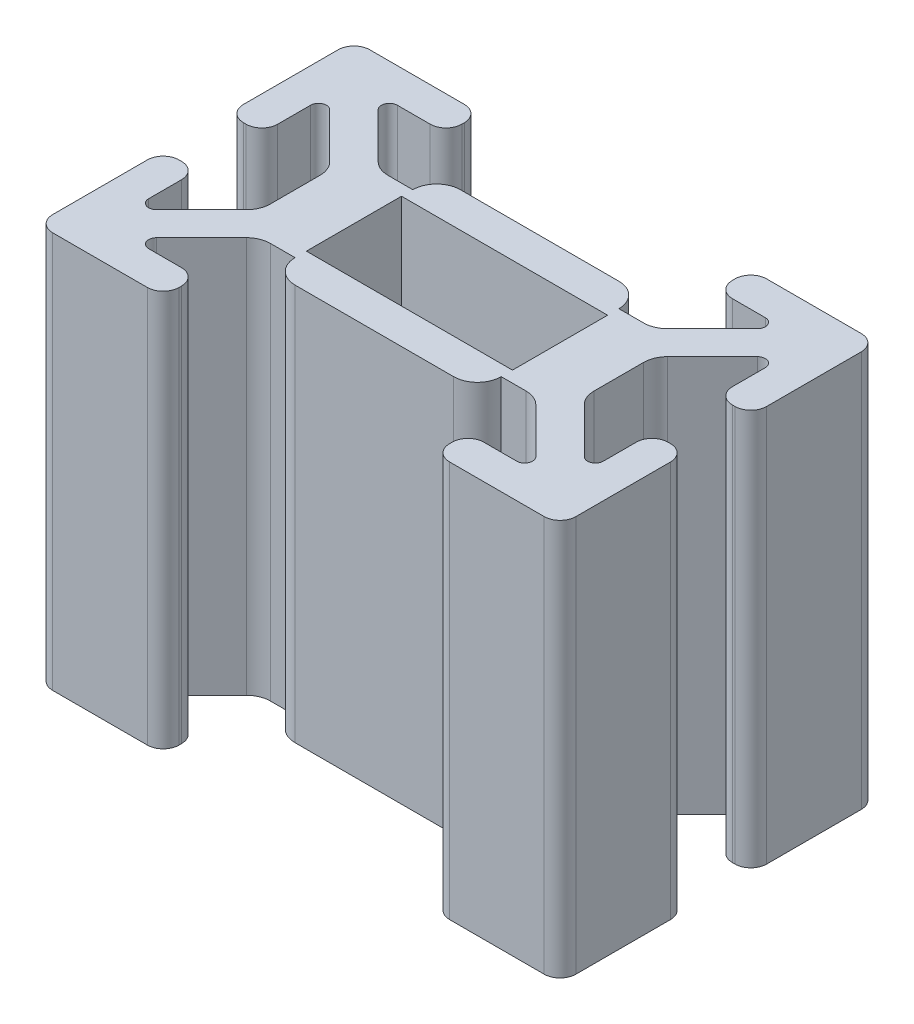
SolidWorks part; units mm, degrees
ref_plane "Front Plane" through (0, 0, 0) normal (0, 0, 1) x (1, 0, 0)
ref_plane "Top Plane" through (0, 0, 0) normal (0, 1, 0) x (1, 0, 0)
ref_plane "Right Plane" through (0, 0, 0) normal (1, 0, 0) x (0, 0, -1)
sketch "Sketch1" plane through (0, 0, 0) normal (0, 1, 0) x (1, 0, 0)
  line L1 (6.065, -20) -> (18, -20)
  line L3 (0, 7.425) -> (0, -7.425)
  line L4 (7.425, -3.1284) -> (7.425, 3.1284)
  line L5 (0, -7.425) -> (3.1284, -7.425)
  line L6 (4.065, -18) -> (4.065, -17.68)
  line L8 (20, -18) -> (20, -6.065)
  line L15 (18, -4.065) -> (17.68, -4.065)
  line L24 (20, 6.065) -> (20, 18)
  line L25 (15.68, 10.2118) -> (15.68, 6.065)
  line L26 (8.3037, 5.2497) -> (13.9729, 10.9189)
  line L27 (5.2497, 8.3037) -> (10.9189, 13.9729)
  line L28 (10.2118, 15.68) -> (6.065, 15.68)
  line L29 (18, 20) -> (6.065, 20)
  line L30 (4.065, 18) -> (4.065, 17.68)
  line L31 (18, 4.065) -> (17.68, 4.065)
  line L32 (0, 7.425) -> (3.1284, 7.425)
  line L33 (20, -18) -> (20, -15.68)
  line L34 (8.3037, -5.2497) -> (13.9729, -10.9189)
  line L40 (5.2497, -8.3037) -> (10.9189, -13.9729)
  line L45 (10.2118, -15.68) -> (6.065, -15.68)
  line L46 (15.68, -10.2118) -> (15.68, -6.065)
  line L47 (-20, -6.065) -> (-20, -18) [skipped]
  line L48 (-15.68, -10.2118) -> (-15.68, -6.065) [skipped]
  line L49 (-8.3037, -5.2497) -> (-13.9729, -10.9189) [skipped]
  line L50 (-5.2497, -8.3037) -> (-10.9189, -13.9729) [skipped]
  line L51 (-10.2118, -15.68) -> (-6.065, -15.68) [skipped]
  line L52 (-18, -20) -> (-6.065, -20) [skipped]
  line L53 (-4.065, -18) -> (-4.065, -17.68) [skipped]
  line L54 (-18, -4.065) -> (-17.68, -4.065) [skipped]
  line L55 (-6.065, 20) -> (-18, 20) [skipped]
  line L56 (-10.2118, 15.68) -> (-6.065, 15.68) [skipped]
  line L57 (-5.2497, 8.3037) -> (-10.9189, 13.9729) [skipped]
  line L58 (-8.3037, 5.2497) -> (-13.9729, 10.9189) [skipped]
  line L59 (-15.68, 10.2118) -> (-15.68, 6.065) [skipped]
  line L60 (-20, 18) -> (-20, 6.065) [skipped]
  line L61 (-18, 4.065) -> (-17.68, 4.065) [skipped]
  line L62 (-4.065, 18) -> (-4.065, 17.68) [skipped]
  arc A1 (18, -20) -> (20, -18) centre (18, -18) ccw
  arc A2 (4.065, -18) -> (6.065, -20) centre (6.065, -18) ccw
  arc A3 (6.065, -15.68) -> (4.065, -17.68) centre (6.065, -17.68) ccw
  arc A4 (17.68, -4.065) -> (15.68, -6.065) centre (17.68, -6.065) ccw
  arc A5 (20, -6.065) -> (18, -4.065) centre (18, -6.065) ccw
  arc A6 (15.68, -10.2118) -> (13.9729, -10.9189) centre (14.68, -10.2118) cw
  arc A7 (10.2118, -15.68) -> (10.9189, -13.9729) centre (10.2118, -14.68) ccw
  arc A8 (3.1284, -7.425) -> (5.2497, -8.3037) centre (3.1284, -10.425) cw
  arc A9 (8.3037, -5.2497) -> (7.425, -3.1284) centre (10.425, -3.1284) cw
  arc A24 (18, 4.065) -> (20, 6.065) centre (18, 6.065) ccw
  arc A25 (15.68, 6.065) -> (17.68, 4.065) centre (17.68, 6.065) ccw
  arc A26 (15.68, 10.2118) -> (13.9729, 10.9189) centre (14.68, 10.2118) ccw
  arc A27 (10.2118, 15.68) -> (10.9189, 13.9729) centre (10.2118, 14.68) cw
  arc A28 (4.065, 17.68) -> (6.065, 15.68) centre (6.065, 17.68) ccw
  arc A29 (6.065, 20) -> (4.065, 18) centre (6.065, 18) ccw
  arc A30 (20, 18) -> (18, 20) centre (18, 18) ccw
  arc A35 (7.425, 3.1284) -> (8.3037, 5.2497) centre (10.425, 3.1284) cw
  arc A36 (5.2497, 8.3037) -> (3.1284, 7.425) centre (3.1284, 10.425) cw
  arc A37 (-18, -4.065) -> (-20, -6.065) centre (-18, -6.065) ccw [skipped]
  arc A38 (-15.68, -6.065) -> (-17.68, -4.065) centre (-17.68, -6.065) ccw [skipped]
  arc A39 (-15.68, -10.2118) -> (-13.9729, -10.9189) centre (-14.68, -10.2118) ccw [skipped]
  arc A40 (-10.2118, -15.68) -> (-10.9189, -13.9729) centre (-10.2118, -14.68) cw [skipped]
  arc A41 (-4.065, -17.68) -> (-6.065, -15.68) centre (-6.065, -17.68) ccw [skipped]
  arc A42 (-6.065, -20) -> (-4.065, -18) centre (-6.065, -18) ccw [skipped]
  arc A43 (-20, -18) -> (-18, -20) centre (-18, -18) ccw [skipped]
  arc A44 (-4.065, 18) -> (-6.065, 20) centre (-6.065, 18) ccw [skipped]
  arc A45 (-6.065, 15.68) -> (-4.065, 17.68) centre (-6.065, 17.68) ccw [skipped]
  arc A46 (-10.2118, 15.68) -> (-10.9189, 13.9729) centre (-10.2118, 14.68) ccw [skipped]
  arc A47 (-15.68, 10.2118) -> (-13.9729, 10.9189) centre (-14.68, 10.2118) cw [skipped]
  arc A48 (-17.68, 4.065) -> (-15.68, 6.065) centre (-17.68, 6.065) ccw [skipped]
  arc A49 (-20, 6.065) -> (-18, 4.065) centre (-18, 6.065) ccw [skipped]
  arc A50 (-18, 20) -> (-20, 18) centre (-18, 18) ccw [skipped]
  arc A51 (-7.425, -3.1284) -> (-8.3037, -5.2497) centre (-10.425, -3.1284) cw [skipped]
  arc A52 (-5.2497, -8.3037) -> (-3.1284, -7.425) centre (-3.1284, -10.425) cw [skipped]
  arc A53 (-3.1284, 7.425) -> (-5.2497, 8.3037) centre (-3.1284, 10.425) cw [skipped]
  arc A54 (-8.3037, 5.2497) -> (-7.425, 3.1284) centre (-10.425, 3.1284) cw [skipped]
  point P13 (0, -20)
  point P31 (0, 0)
  point P44 (0, 0)
  point P68 (15.68, -12.626)
  point P71 (12.626, -15.68)
  point P121 (0, 0)
  point P144 (0, 0)
  dimension "D1" = 2
  dimension "D3" = 2
  dimension "D7" = 1
  dimension "D5" = 3
  dimension "D6" = 4
  dimension "D8" = 4
extrude "Boss-Extrude3" add sketch "Sketch1" along normal blind 50 contours L27 A36 L32 L3 L5 A8 L40 A7 L45 A3 L6 A2 L1 A1 L8 A5 L15 A4 L46 A6 L34 A9 L4 A35 L26 A26 L25 A25 L31 A24 L24 A30 L29 A29 L30 A28 L28 A27 region at (4.967, 0, 19.098)
sketch "Sketch4" plane through (0, 0, 0) normal (-1, 0, 0) x (0, 0, 1)
  line L0 (7.425, 50) -> (7.425, 0) construction
  line L1 (-7.425, 0) -> (7.425, 0)
  line L2 (-7.425, 0) -> (-7.425, 5)
  line L3 (-7.425, 5) -> (7.425, 5)
  line L4 (7.425, 0) -> (7.425, 5)
extrude "Boss-Extrude4" add sketch "Sketch4" along normal blind 26
ref_plane "Plane2" through (-13, 0, 0) normal (-1, 0, 0) x (0, 0, 1)
mirror "Mirror2" about plane through (-13, 0, 0) normal (-1, 0, 0) of "Boss-Extrude3"
sketch "Sketch6" plane through (0, 0, 7.425) normal (0, 0, 1) x (1, 0, 0)
  line L1 (-26, 5) -> (0, 5)
  line L2 (-26, 5) -> (-26, 0)
  line L3 (-26, 0) -> (0, 0)
  line L4 (0, 5) -> (0, 0)
extrude "Boss-Extrude5" add sketch "Sketch6" along normal blind 3
sketch "Sketch7" plane through (0, 0, -7.425) normal (0, 0, -1) x (-1, 0, 0)
  line L0 (29.1284, 0) -> (-3.1284, 0) construction
  line L1 (0, 5) -> (26, 5)
  line L2 (0, 5) -> (0, 0)
  line L3 (0, 0) -> (26, 0)
  line L4 (26, 5) -> (26, 0)
extrude "Boss-Extrude6" add sketch "Sketch7" along normal blind 3
sketch "Sketch8" plane through (0, 5, 0) normal (0, 1, 0) x (1, 0, 0)
  line L0 (0, 10.425) -> (0, 7.425) construction
  line L1 (-23, 10.425) -> (-3, 10.425)
  line L2 (-26, 7.425) -> (-26, 6)
  line L3 (-26, 6) -> (0, 6)
  line L4 (0, 7.425) -> (0, 6)
  line L5 (-26, 0) -> (-21.9895, 0)
  line L6 (-26, -7.425) -> (-26, 7.425) construction
  line L7 (0, -7.425) -> (0, -6)
  line L8 (-26, -6) -> (0, -6)
  line L9 (-26, -7.425) -> (-26, -6)
  line L10 (-23, -10.425) -> (-3, -10.425)
  line L14 (0, 7.425) -> (0, 10.425)
  arc A0 (-26, -7.425) -> (-23, -10.425) centre (-23, -7.425) ccw
  arc A1 (-3, -10.425) -> (0, -7.425) centre (-3, -7.425) ccw
  arc A2 (0, 7.425) -> (-3, 10.425) centre (-3, 7.425) ccw
  arc A3 (-23, 10.425) -> (-26, 7.425) centre (-23, 7.425) ccw
  point P20 (-26, -10.425)
  point P23 (0, -10.425)
  point P29 (-26, 10.425)
  line M1 (0, -7.425) -> (0, 7.425)
  line M2 (0, 7.425) -> (0, 10.425)
  line M3 (0, 10.425) -> (-26, 10.425)
  line M4 (-26, 10.425) -> (-26, 7.425)
  line M5 (-26, 7.425) -> (-26, -7.425)
  line M6 (-26, -7.425) -> (-26, -10.425)
  line M7 (-26, -10.425) -> (0, -10.425)
  line M8 (0, -10.425) -> (0, -7.425)
  dimension "D1" = 3
extrude "Boss-Extrude7" add sketch "Sketch8" along normal blind 45 contours L8 M5 M6 M7 M8 M1 | L3 M5 M1 M2 M3 M4 region at (-13, 5, -8.1589) region at (-13, 5, 8.1589)
sketch "Sketch9" plane through (0, 5, 0) normal (0, 1, 0) x (1, 0, 0)
  line L0 (-3, -10.425) -> (0, -10.425)
  line L1 (-26, 10.425) -> (-26, 7.425) construction
  line L2 (0, -10.425) -> (0, -7.425)
  line L3 (-26, -10.425) -> (-26, -7.425)
  line L4 (-23, -10.425) -> (-26, -10.425)
  line L5 (0, 10.425) -> (0, 7.425)
  line L6 (-3, 10.425) -> (0, 10.425)
  line L7 (0, 0) -> (-5.6758, 0)
  line L8 (-23, 10.425) -> (-26, 10.425)
  line L9 (-26, 10.425) -> (-26, 7.425)
  line L10 (0, -6) -> (0, 6) construction
  arc A0 (-23, 10.425) -> (-26, 7.425) centre (-23, 7.425) ccw construction
  arc A1 (-23, 10.425) -> (-26, 7.425) centre (-23, 7.425) ccw
  arc A2 (-3, 10.425) -> (0, 7.425) centre (-3, 7.425) cw
  arc A3 (-3, -10.425) -> (0, -7.425) centre (-3, -7.425) ccw
  arc A4 (-23, -10.425) -> (-26, -7.425) centre (-23, -7.425) cw
  point P20 (-26, 10.425)
  arc M1 (-26, 7.425) -> (-23, 10.425) centre (-23, 7.425) cw
  line M2 (-23, 10.425) -> (-26, 10.425)
  line M3 (-26, 10.425) -> (-26, 7.425)
  dimension "D1" = 3
extrude "Cut-Extrude1" cut sketch "Sketch9" against normal blind 5 contours L4 A4 L3 | A3 L0 L2 | L6 A2 L5 | M3 M1 M2 region at (-0.6701, 5, 9.7549) region at (-25.3299, 5, 9.7549) region at (-0.6701, 5, -9.7549) region at (-25.3299, 5, -9.7549)
